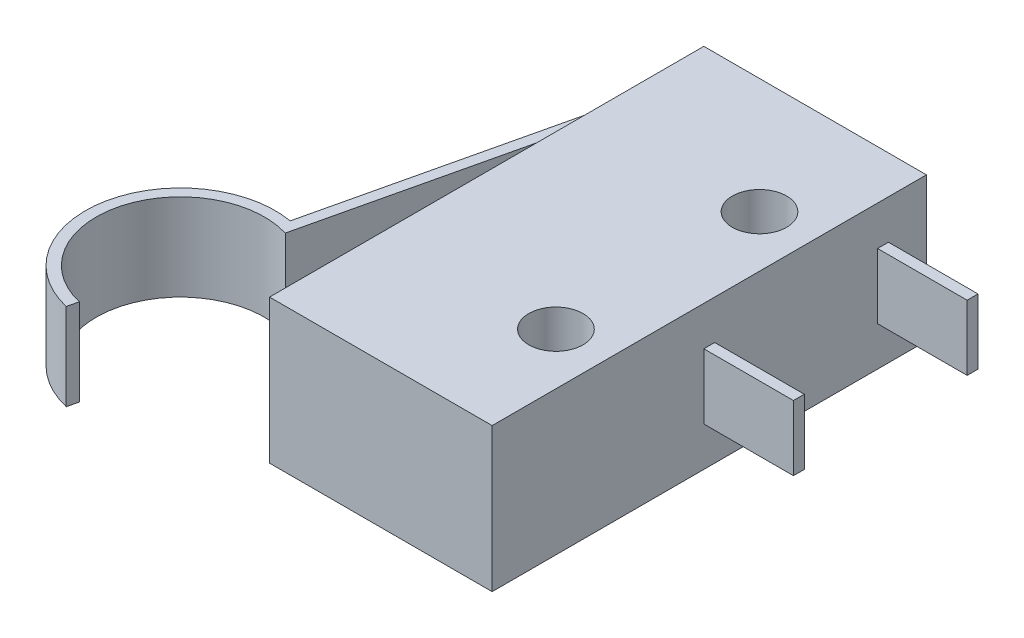
SolidWorks part; units mm, degrees
ref_plane "Front Plane" through (0, 0, 0) normal (0, 0, 1) x (1, 0, 0)
ref_plane "Top Plane" through (0, 0, 0) normal (0, 1, 0) x (1, 0, 0)
ref_plane "Right Plane" through (0, 0, 0) normal (1, 0, 0) x (0, 0, -1)
sketch "Sketch1" plane through (0, 0, 0) normal (0, 1, 0) x (1, 0, 0)
  line L0 (2.794, 4.7625) -> (2.794, -4.7625) construction
  line L1 (5.207, 10.16) -> (-5.207, 10.16)
  line L2 (5.207, 10.16) -> (5.207, -10.16)
  line L3 (5.207, -10.16) -> (-5.207, -10.16)
  line L4 (-5.207, 10.16) -> (-5.207, -10.16)
  line L5 (5.207, 10.16) -> (-5.207, -10.16) construction
  line L6 (5.207, -10.16) -> (-5.207, 10.16) construction
  line L7 (-5.207, 7.239) -> (-5.969, 7.239) construction
  line L8 (5.207, -0.254) -> (9.398, -0.254)
  line L9 (5.207, -0.254) -> (5.207, 0.254)
  line L10 (5.207, 0.254) -> (9.398, 0.254)
  line L11 (9.398, -0.254) -> (9.398, 0.254)
  line L12 (5.207, 7.874) -> (9.398, 7.874)
  line L13 (5.207, 7.874) -> (5.207, 8.382)
  line L14 (5.207, 8.382) -> (9.398, 8.382)
  line L15 (9.398, 7.874) -> (9.398, 8.382)
  line L16 (-5.969, 7.239) -> (-8.9537, -5.5532) construction
  line L17 (-8.9537, -5.5532) -> (-10.8583, -13.716) construction
  line L18 (-5.207, 7.493) -> (-6.1706, 7.493)
  line L19 (-6.1706, 7.493) -> (-9.145, -5.2552)
  line L20 (-5.207, 6.985) -> (-5.7674, 6.985)
  line L21 (-5.7674, 6.985) -> (-8.7659, -5.8663)
  line L22 (-10.8006, -13.4686) -> (-10.916, -13.9634)
  circle A0 centre (2.794, 4.7625) radius 1.27
  circle A1 centre (2.794, -4.7625) radius 1.27
  arc A2 (-8.9537, -5.5532) -> (-10.8583, -13.716) centre (-9.906, -9.6346) ccw construction
  arc A3 (-9.145, -5.2552) -> (-10.916, -13.9634) centre (-9.906, -9.6346) ccw
  arc A4 (-8.7659, -5.8663) -> (-10.8006, -13.4686) centre (-9.906, -9.6346) ccw
  point P0 (0, 0)
  point P9 (2.794, 0)
  point P19 (9.398, 0)
  point P24 (-14.097, -9.6346)
  dimension "D3" = 2.54
  dimension "D11" = 4.191
  dimension "D1" = 20.32
  dimension "D2" = 10.414
  dimension "D4" = 9.525
  dimension "D5" = 8.001
  dimension "D6" = 0.508
  dimension "D7" = 4.191
  dimension "D8" = 1.778
  dimension "D9" = 8.89
  dimension "D10" = 2.921
  dimension "D12" = 0.762
  dimension "D13" = 3.556
  dimension "D14" = 0.254
  dimension "D15" = 0.254
extrude "Boss-Extrude1" add sketch "Sketch1" along normal mid plane 6.731 contours L1 L4 L3 L2 A1 A0 region at (-0.1405, 0, 0)
extrude "Boss-Extrude2" add sketch "Sketch1<3>" along normal mid plane 3.048 contours L8 L11 L10 L2 | L12 L15 L14 L2 region at (7.3025, 0, -8.128) region at (7.3025, 0, 0)
sketch "Sketch1<3>" plane through (0, 0, 0) normal (0, 1, 0) x (1, 0, 0) same geometry as "Sketch1"
extrude "Boss-Extrude3" add sketch "Sketch1<4>" along normal mid plane 4.064 contours A4 L21 L20 L4 L18 L19 A3 L22 region at (-5.4402, 0, -7.239)
sketch "Sketch1<4>" plane through (0, 0, 0) normal (0, 1, 0) x (1, 0, 0) same geometry as "Sketch1"
